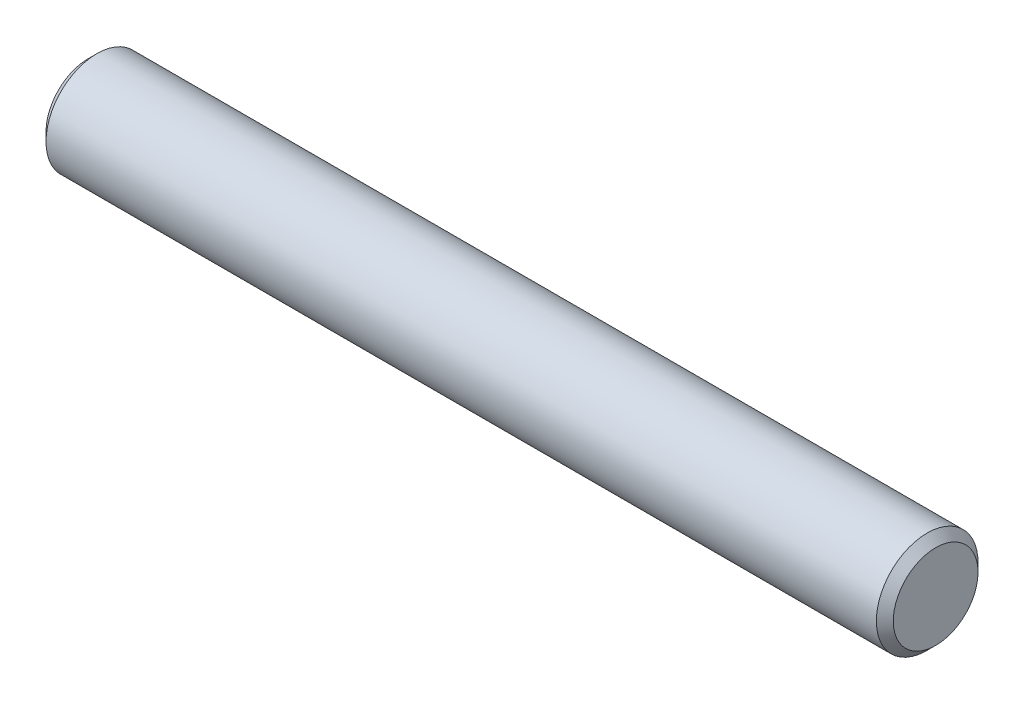
SolidWorks part; units mm, degrees
material "Copper"
ref_plane "Front Plane" through (0, 0, 0) normal (0, 0, 1) x (1, 0, 0)
ref_plane "Top Plane" through (0, 0, 0) normal (0, 1, 0) x (1, 0, 0)
ref_plane "Right Plane" through (0, 0, 0) normal (1, 0, 0) x (0, 0, -1)
sketch "Sketch1" plane through (0, 0, 0) normal (0, 0, 1) x (1, 0, 0)
  line L0 (0, 0) -> (0, 3)
  line L1 (0, 3) -> (50, 3)
  line L2 (50, 3) -> (50, 0)
  line L3 (50, 0) -> (0, 0)
  dimension "D1" = 50
  dimension "D2" = 3
revolve "Revolve1" add sketch "Sketch1" angle 360 about L3
chamfer "Chamfer1" distance 0.5 angle 45 2 edges at (0, 3, 0) (50, 3, 0)
sketch "Sketch2" plane through (50, 0, 0) normal (1, 0, 0) x (0, 0, -1)
  point P0 (0, 0)
sketch "Sketch3" plane through (0, 0, 0) normal (-1, 0, 0) x (0, 0, 1)
  point P0 (0, 0)
ref_axis "Axis1" through (0, 0, 0) along (1, 0, 0)
